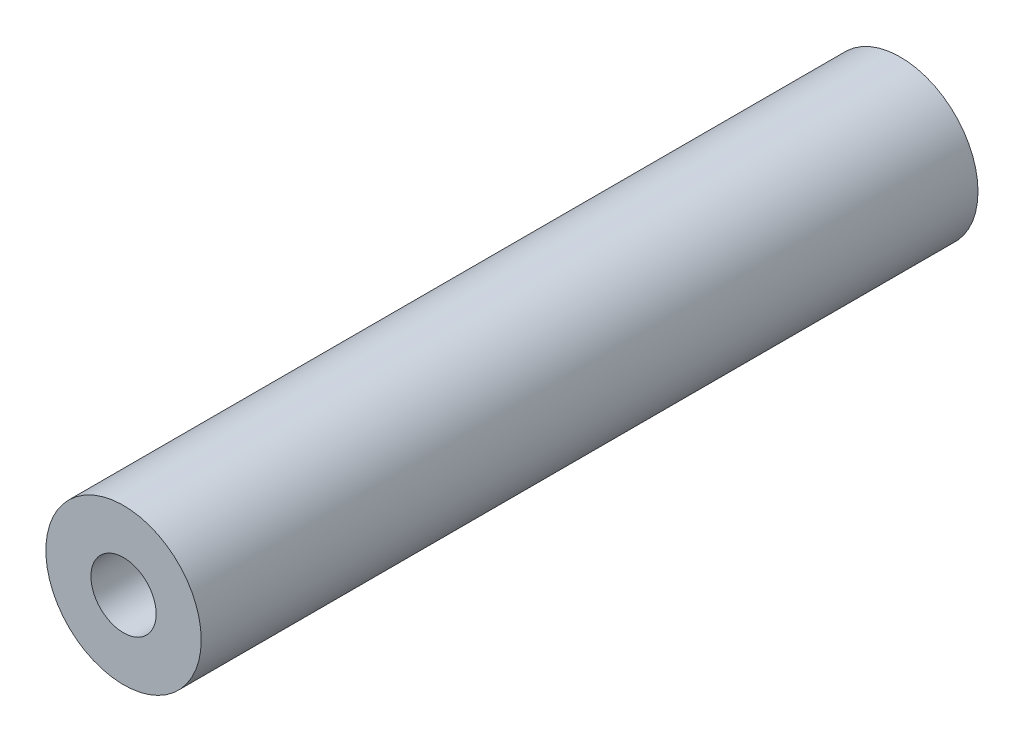
SolidWorks part; units mm, degrees
ref_plane "Спереди" through (0, 0, 0) normal (0, 0, 1) x (1, 0, 0)
ref_plane "Сверху" through (0, 0, 0) normal (0, 1, 0) x (1, 0, 0)
ref_plane "Справа" through (0, 0, 0) normal (1, 0, 0) x (0, 0, -1)
sketch "Эскиз1" plane through (0, 0, 0) normal (0, 0, 1) x (1, 0, 0)
  circle A0 centre (0, 0) radius 5
  dimension "D1" = 10
extrude "Бобышка-Вытянуть1" add sketch "Эскиз1" along normal blind 50
hole_wizard "Отверстие обработанное метчиком M5x0.81" positions "Эскиз3" profile "Эскиз2" tap size "M5x0.8" standard "Ansi Metric" end condition through all
sketch "Эскиз3" plane through (0, 0, 50) normal (0, 0, 1) x (1, 0, 0)
  point P0 (0, 0)
sketch "Эскиз2" plane through (0, 0, 50) normal (1, 0, 0) x (0, -1, 0)
  line L0 (0, 0) -> (0, 50)
  line L1 (0, 50) -> (2.1, 50)
  line L2 (2.1, 50) -> (2.1, 0)
  line L5 (2.1, 0) -> (0, 0)
  line L11 (0, -6.35) -> (0, 107.95) construction
  dimension "Диаметр проходного сверла" = 4.2
  dimension "Глубина проходного сверла" = 50
cosmetic thread "Отверстие резьбы1" parameters "D2"=5
